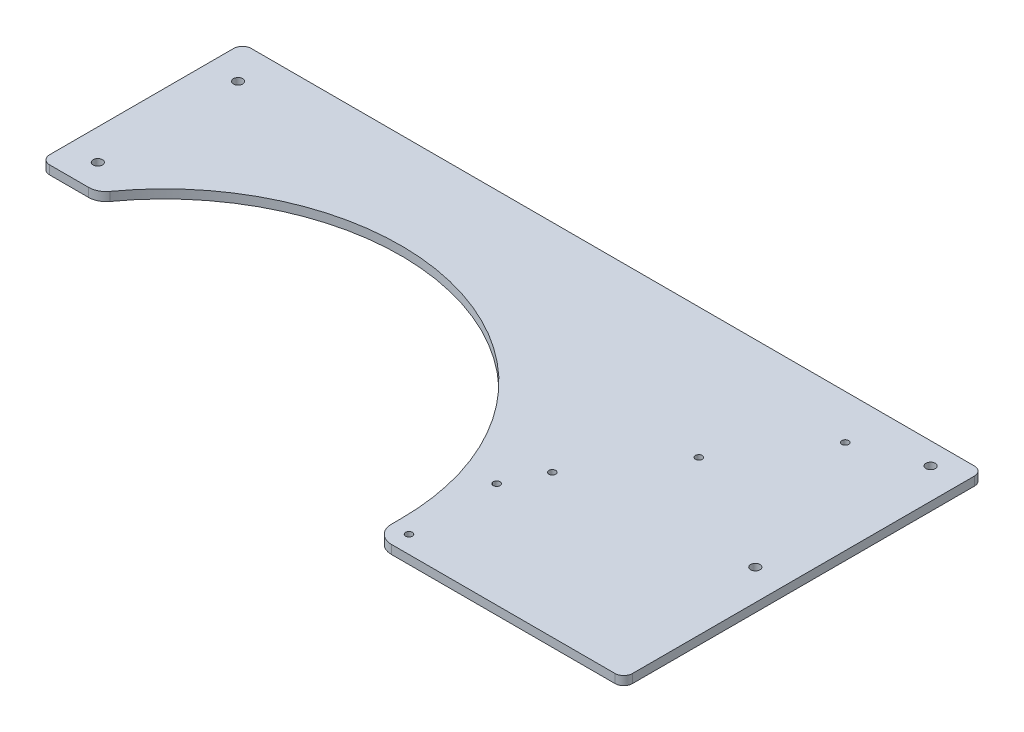
SolidWorks part; units mm, degrees
material "PE High Density"
ref_plane "Front Plane" through (0, 0, 0) normal (0, 0, 1) x (1, 0, 0)
ref_plane "Top Plane" through (0, 0, 0) normal (0, 1, 0) x (1, 0, 0)
ref_plane "Right Plane" through (0, 0, 0) normal (1, 0, 0) x (0, 0, -1)
sketch "Sketch1" plane through (0, 0, 0) normal (0, 1, 0) x (1, 0, 0)
  line L0 (-268.2875, -15.875) -> (-233.3625, -15.875)
  line L1 (-227.0125, -130.175) -> (268.2875, -130.175)
  line L2 (-268.2875, -15.875) -> (-268.2875, 130.175)
  line L3 (-268.2875, 130.175) -> (268.2875, 130.175)
  line L4 (268.2875, -130.175) -> (268.2875, 130.175)
  line L5 (-268.2875, -130.175) -> (268.2875, 130.175) construction
  line L6 (-268.2875, 130.175) -> (268.2875, -130.175) construction
  line L7 (-227.0125, -22.225) -> (-227.0125, -130.175)
  arc A0 (-233.3625, -15.875) -> (-227.0125, -22.225) centre (-233.3625, -22.225) cw
  point P0 (0, 0)
  point P14 (-227.0125, -15.875)
  dimension "D5" = 6.35
  dimension "D1" = 536.575
  dimension "D2" = 260.35
  dimension "D3" = 41.275
  dimension "D4" = 114.3
extrude "Boss-Extrude1" add sketch "Sketch1" along normal blind 6.35
sketch "Sketch2" plane through (0, 6.35, 0) normal (0, 1, 0) x (1, 0, 0)
  line L0 (-227.0125, -130.175) -> (268.2875, -130.175) construction
  line L1 (-227.0125, -22.225) -> (-227.0125, -130.175) construction
  line L2 (268.2875, -130.175) -> (268.2875, 130.175) construction
  line L3 (-268.2875, 130.175) -> (-268.2875, -15.875) construction
  line L4 (268.2875, 130.175) -> (-268.2875, 130.175) construction
  line L5 (200.4456, 98.1535) -> (113.0325, -26.6852) construction
  line L6 (100.0125, -53.975) -> (100.0125, -117.475) construction
  point P0 (-220.6625, -117.475)
  point P1 (-220.6625, -53.975)
  point P2 (-246.0625, 3.175)
  point P3 (-246.0625, 104.775)
  point P12 (246.0625, 114.3381)
  point P13 (246.0625, -12.6619)
  point P16 (100.0125, -53.975)
  point P17 (100.0125, -117.475)
  point P18 (113.0325, -26.6852)
  point P19 (156.7391, 35.7341)
  point P20 (200.4456, 98.1535)
  dimension "D1" = 63.5
  dimension "D2" = 12.7
  dimension "D3" = 6.35
  dimension "D4" = 101.6
  dimension "D5" = 25.4
  dimension "D6" = 22.225
  dimension "D7" = 127
  dimension "D8" = 22.225
  dimension "D9" = 15.8369
  dimension "D10" = 152.4
  dimension "D11" = 63.5
  dimension "D12" = 12.7
  dimension "D13" = 145
  dimension "D14" = 168.275
  dimension "D15" = 13.02
  dimension "D16" = 103.4898
hole_wizard "17/64 (0.26563) Diameter Hole1" positions "Sketch3" profile "Sketch4" hole size "17/64" standard "ANSI Inch" end condition through all
sketch "Sketch3" plane through (0, 6.35, 0) normal (0, 1, 0) x (1, 0, 0)
  point P0 (-246.0625, 104.775)
  point P3 (-246.0625, 3.175)
  point P6 (-220.6625, -53.975)
  point P9 (-220.6625, -117.475)
  point P14 (246.0625, 114.3381)
  point P17 (246.0625, -12.6619)
sketch "Sketch4" plane through (-246.0625, 6.35, -104.775) normal (1, 0, 0) x (0, 0, 1)
  line L0 (0, 0) -> (0, 6.35)
  line L1 (0, 6.35) -> (3.3735, 6.35)
  line L2 (3.3735, 6.35) -> (3.3735, 0)
  line L5 (3.3735, 0) -> (0, 0)
  line L11 (0, -6.35) -> (0, 107.95) construction
  dimension "Thru Hole Dia." = 6.747
  dimension "Thru Hole Depth" = 6.35
fillet "Fillet1" radius 6.35 5 edges at (268.2875, 3.175, -130.175) (268.2875, 3.175, 130.175) (-227.0125, 3.175, 130.175) (-268.2875, 3.175, 15.875) (-268.2875, 3.175, -130.175)
hole_wizard "#10 (0.1935) Diameter Hole1" positions "Sketch6" profile "Sketch7" hole size "#10" standard "ANSI Inch" end condition through all
sketch "Sketch6" plane through (0, 6.35, 0) normal (0, 1, 0) x (1, 0, 0)
  point P0 (200.4456, 98.1535)
  point P3 (156.7391, 35.7341)
  point P6 (113.0325, -26.6852)
  point P9 (100.0125, -53.975)
  point P12 (100.0125, -117.475)
sketch "Sketch7" plane through (200.4456, 6.35, -98.1535) normal (1, 0, 0) x (0, 0, 1)
  line L0 (0, 0) -> (0, 6.35)
  line L1 (0, 6.35) -> (2.4574, 6.35)
  line L2 (2.4574, 6.35) -> (2.4574, 0)
  line L5 (2.4574, 0) -> (0, 0)
  line L11 (0, -6.35) -> (0, 107.95) construction
  dimension "Thru Hole Dia." = 4.9149
  dimension "Thru Hole Depth" = 6.35
sketch "Sketch8" plane through (0, 6.35, 0) normal (0, 1, 0) x (1, 0, 0)
  line L0 (87.3125, -130.175) -> (87.3125, -110.6476)
  line L1 (-220.6625, -130.175) -> (261.9375, -130.175) construction
  line L2 (-233.3625, -15.875) -> (-227.0125, -15.875)
  line L3 (-227.0125, -22.225) -> (-227.0125, -123.825) construction
  line L4 (-220.6625, -130.175) -> (261.9375, -130.175)
  line L5 (-227.0125, -22.225) -> (-227.0125, -123.825)
  arc A0 (-227.0125, -15.875) -> (87.3125, -110.6476) centre (-84.1375, -110.6476) cw
  circle A1 centre (100.0125, -117.475) radius 2.4574 construction
  arc A2 (-227.0125, -123.825) -> (-220.6625, -130.175) centre (-220.6625, -123.825) ccw construction
  arc A3 (-227.0125, -22.225) -> (-233.3625, -15.875) centre (-233.3625, -22.225) ccw construction
  arc A4 (-227.0125, -123.825) -> (-220.6625, -130.175) centre (-220.6625, -123.825) ccw
  arc A5 (-227.0125, -22.225) -> (-233.3625, -15.875) centre (-233.3625, -22.225) ccw
  circle M9 centre (-220.6625, -53.975) radius 3.3735
  circle M10 centre (-220.6625, -117.475) radius 3.3735
  arc M20 (-233.3625, -15.875) -> (-227.0125, -22.225) centre (-233.3625, -22.225) cw
  line M21 (-227.0125, -22.225) -> (-227.0125, -123.825)
  arc M22 (-227.0125, -123.825) -> (-220.6625, -130.175) centre (-220.6625, -123.825) ccw
  line M23 (-220.6625, -130.175) -> (261.9375, -130.175)
  dimension "D1" = 171.45
  dimension "D2" = 12.7
  dimension "D3" = 0
extrude "Cut-Extrude1" cut sketch "Sketch8" against normal through all contours A0 L2 L0 M20 M21 M22 M23 M9 M10 region at (-76.5748, 6.35, 46.5036)
fillet "Fillet2" radius 12.7 2 edges at (87.3125, 3.175, 130.175) (-227.0125, 3.175, 15.875)
